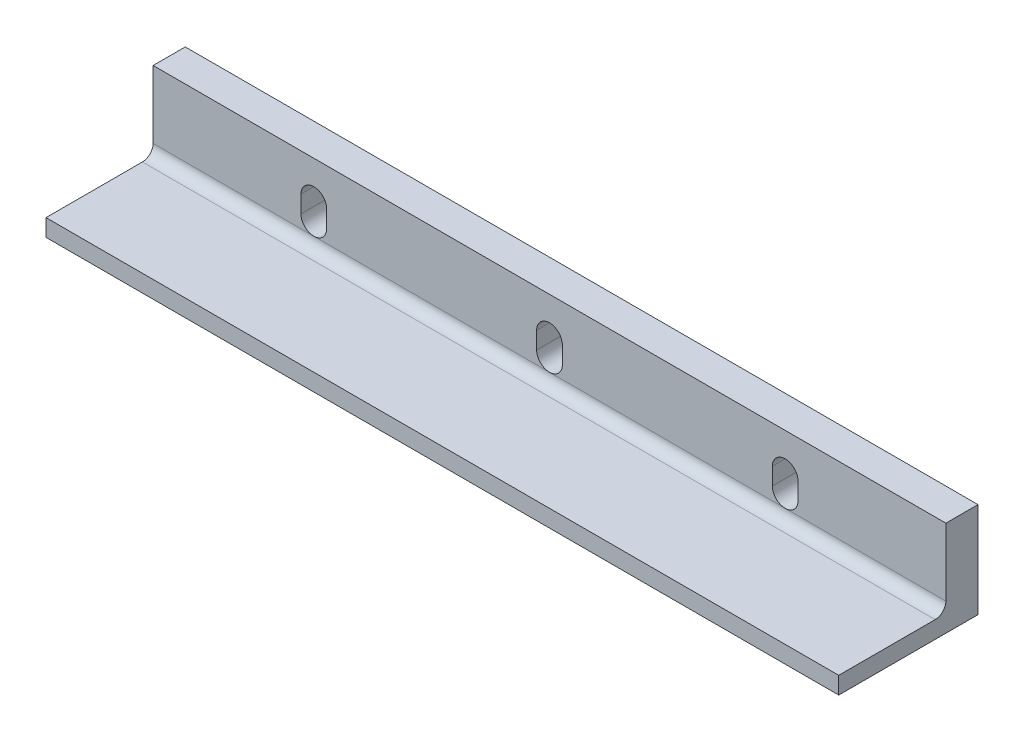
SolidWorks part; units mm, degrees
ref_plane "Front Plane" through (0, 0, 0) normal (0, 0, 1) x (1, 0, 0)
ref_plane "Top Plane" through (0, 0, 0) normal (0, 1, 0) x (1, 0, 0)
ref_plane "Right Plane" through (0, 0, 0) normal (1, 0, 0) x (0, 0, -1)
sketch "Sketch1" plane through (0, 0, 0) normal (0, 1, 0) x (1, 0, 0)
  line L1 (-37, -6.5) -> (37, -6.5)
  line L2 (-37, -6.5) -> (-37, 6.5)
  line L3 (-37, 6.5) -> (37, 6.5)
  line L4 (37, -6.5) -> (37, 6.5)
  line L5 (-37, -6.5) -> (37, 6.5) construction
  line L6 (-37, 6.5) -> (37, -6.5) construction
  point P0 (0, 0)
  dimension "D1" = 13
  dimension "D2" = 74
extrude "Boss-Extrude1" add sketch "Sketch1" along normal blind 1.6
sketch "Sketch2" plane through (0, 1.6, 0) normal (0, 1, 0) x (1, 0, 0)
  line L0 (37, -6.5) -> (37, 6.5) construction
  line L1 (-37, 6.5) -> (37, 6.5)
  line L2 (-37, 6.5) -> (-37, 3.5)
  line L3 (-37, 3.5) -> (37, 3.5)
  line L4 (37, 6.5) -> (37, 3.5)
  dimension "D1" = 3
extrude "Boss-Extrude2" add sketch "Sketch2" along normal blind 7.3
fillet "Fillet1" radius 1 1 edges at (0, 1.6, -3.5)
sketch "Sketch3" plane through (0, 0, -6.5) normal (0, 0, 1) x (1, 0, 0)
  line L0 (0, 0) -> (0, 4.6) construction
  line L1 (22, 4.6) -> (-22, 4.6) construction
  point P6 (0, 4.6)
  dimension "D1" = 4.6
  dimension "D2" = 44
hole_wizard "M2 Clearance Slot1" positions "Sketch7" profile "Sketch8" size "M2" standard "ANSI Metric" slot yes end condition through all
sketch "Sketch7" plane through (0, 0, -3.5) normal (0, 0, 1) x (1, 0, 0)
  line L0 (-22, 2.6) -> (-22, 6.6) construction
  point P14 (-22, 4.6)
  point P19 (0, 4.6)
  point P22 (22, 4.6)
  point P26 (0, 0)
  dimension "D1" = 4
sketch "Sketch8" plane through (-22, 4.6, -3.5) normal (1, 0, 0) x (0, -1, 0)
  line L0 (0, 0) -> (0, 3)
  line L1 (0, 3) -> (1.2, 3)
  line L2 (1.2, 3) -> (1.2, 0)
  line L5 (1.2, 0) -> (0, 0)
  line L11 (0, -6.35) -> (0, 107.95) construction
  dimension "Thru Hole Dia." = 2.4
  dimension "Thru Hole Depth" = 3
